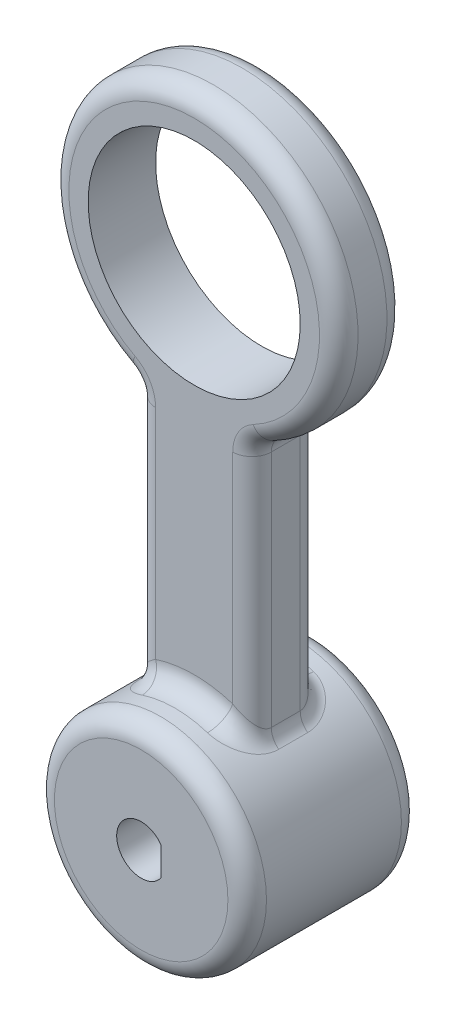
SolidWorks part; units mm, degrees
ref_plane "前视基准面" through (0, 0, 0) normal (0, 0, 1) x (1, 0, 0)
ref_plane "上视基准面" through (0, 0, 0) normal (0, 1, 0) x (1, 0, 0)
ref_plane "右视基准面" through (0, 0, 0) normal (1, 0, 0) x (0, 0, -1)
sketch "草图1" plane through (0, 0, 0) normal (0, 0, 1) x (1, 0, 0)
  line L0 (0, 25) -> (0, -25) construction
  line L1 (6, 25) -> (6, -25)
  line L2 (-6, 25) -> (-6, -25)
  line L3 (2.08, -23.5422) -> (2.08, -26.4578)
  arc A0 (6, 25) -> (-6, 25) centre (0, 25) ccw
  arc A1 (-6, -25) -> (6, -25) centre (0, -25) ccw
  circle A2 centre (0, 25) radius 11
  circle A3 centre (0, 25) radius 15
  circle A4 centre (0, -25) radius 11
  circle A5 centre (0, -25) radius 2.54
  point P3 (0, 0)
  dimension "D3" = 6
  dimension "D4" = 5.08
  dimension "D5" = 22
  dimension "D6" = 6
  dimension "D1" = 0
  dimension "D2" = 50
  dimension "D7" = 3.92
extrude "凸台-拉伸1" add sketch "草图1" along normal mid plane 7 contours L1 A3 L2 A2 | L0 A3 L2 A4 | L0 A2 L2 A3 | A2 L0 A3 L1 | A3 L0 A4 L1 region at (3.0608, 12.5079, 0) region at (-3.0608, 12.5079, 0) region at (3.0598, -2.0841, 0) region at (-3.0598, -2.0841, 0) region at (-6.4155, 13.5164, 0)
extrude "凸台-拉伸3" add sketch "草图1<4>" along normal mid plane 18 contours L1 A4 A5 L2 A1 | L2 A4 L1 A1 | L3 A5 region at (9.4069, -19.8984, 0) region at (0, -21.8403, 0) region at (2.2655, -25, 0)
sketch "草图1<4>" plane through (0, 0, 0) normal (0, 0, 1) x (1, 0, 0) same geometry as "草图1"
fillet "圆角1" radius 2 14 edges at (6, 11.2523, 0) (0, 40, 3.5) (-6, 11.2523, 0) (0, 40, -3.5) (11, -25, -9) (11, -25, 9) (6, -15.7805, 0) (0, -14, -3.5) (-6, -15.7805, 0) (0, -14, 3.5) (-6, -2.2641, -3.5) (6, -2.2641, -3.5) (-6, -2.2641, 3.5) (6, -2.2641, 3.5)
